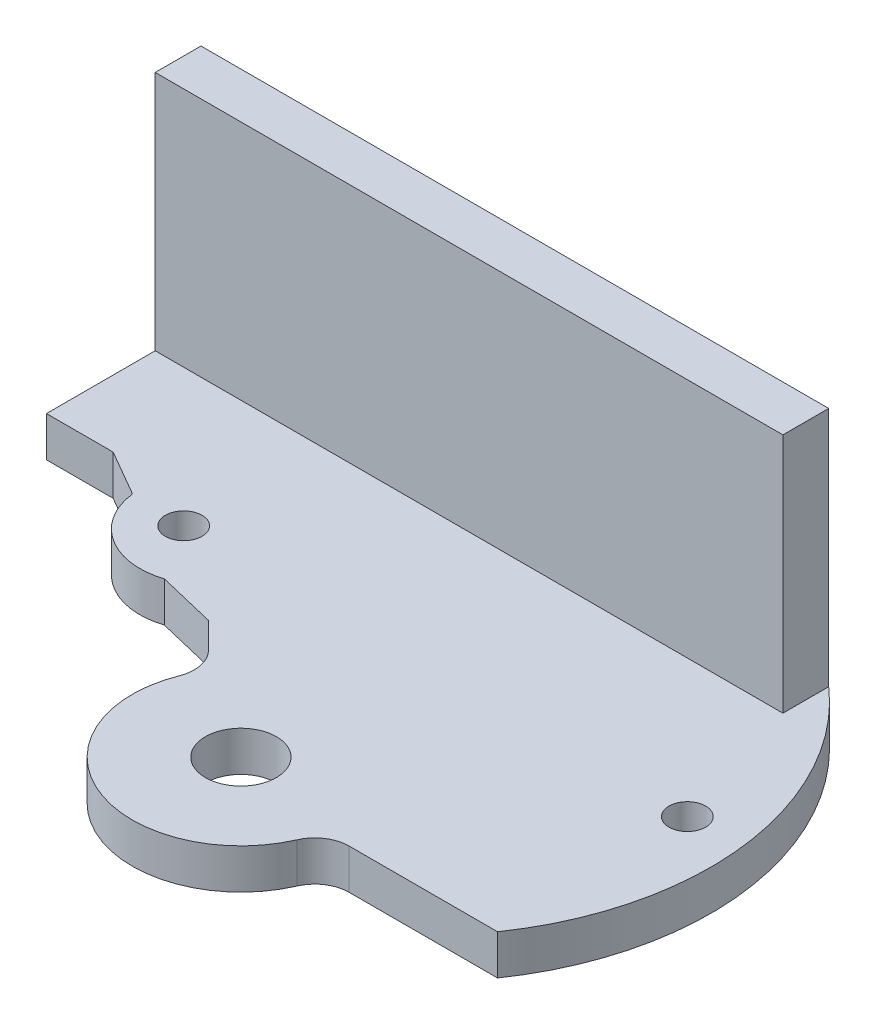
SolidWorks part; units mm, degrees
ref_plane "Alzado" through (0, 0, 0) normal (0, 0, 1) x (1, 0, 0)
ref_plane "Planta" through (0, 0, 0) normal (0, 1, 0) x (1, 0, 0)
ref_plane "Vista lateral" through (0, 0, 0) normal (1, 0, 0) x (0, 0, -1)
sketch "Croquis1" plane through (0, 0, 0) normal (0, 1, 0) x (1, 0, 0)
  line L0 (-35, 32.5) -> (35, -32.5) construction
  line L1 (-35, 32.5) -> (35, 32.5)
  line L2 (-35, 32.5) -> (-35, -32.5)
  line L3 (-35, -32.5) -> (35, -32.5)
  line L4 (35, 32.5) -> (35, -32.5)
  dimension "D1" = 70
  dimension "D2" = 65
extrude "Extruir1" add sketch "Croquis1" along normal blind 3.5
sketch "Croquis2" plane through (0, 3.5, 0) normal (0, 1, 0) x (1, 0, 0)
  line L0 (0, 32.5) -> (0, -32.5) construction
  line L1 (35, 32.5) -> (-35, 32.5) construction
  line L2 (-35, -32.5) -> (35, -32.5) construction
  circle A0 centre (0, -17.5) radius 3.1
  dimension "D1" = 6.2
  dimension "D2" = 15
extrude "Extruir2" cut sketch "Croquis2" against normal blind 5
sketch "Croquis3" plane through (0, 3.5, 0) normal (0, 1, 0) x (1, 0, 0)
  line L0 (0, -32.5) -> (0, 32.5) construction
  line L1 (-35, -32.5) -> (35, -32.5) construction
  line L2 (35, 32.5) -> (-35, 32.5) construction
  line L3 (-32.9868, -32.5) -> (-32.9868, 32.5) construction
  line L4 (-32.9868, 1.5) -> (-12.9615, 1.5)
  line L5 (18.8496, -32.5) -> (18.8496, 32.5) construction
  line L6 (-32.9868, 3.5) -> (18.8496, 3.5) construction
  line L7 (-32.9868, 2) -> (0, 2) construction
  line L8 (-32.9868, 11.5) -> (18.8496, 11.5) construction
  line L9 (0, -17.5) -> (-14.8492, -2.6508) construction
  line L10 (0, -17.5) -> (14.8492, -2.6508) construction
  line L11 (0, 2) -> (18.8496, 2) construction
  line L12 (-32.9868, 2) -> (18.8496, 2) construction
  line L13 (-32.9868, 12) -> (18.8496, 12)
  line L14 (-5.3033, -12.1967) -> (-16.2635, -1.2365) construction
  line L15 (12.9615, 1.5) -> (18.8496, 1.5)
  line L16 (-32.9868, 1.5) -> (18.8496, 1.5) construction
  line L17 (7.9844, -18) -> (22.9946, -18)
  line L18 (-5.9993, -12.2078) -> (-16.6132, -1.5939)
  line L19 (0, -17.5) -> (23, -17.5) construction
  line L20 (7.5, -17.5) -> (23, -17.5) construction
  line L21 (-5.6569, -12.5503) -> (-16.617, -1.5901) construction
  line L22 (7.5, -18) -> (23, -18) construction
  line L23 (-32.9868, 12) -> (-32.9868, 1.5)
  line L24 (18.8496, 12) -> (18.8496, 1.5)
  line L25 (-34.4868, 13.5) -> (20.3496, 13.5)
  line L26 (20.3496, 13.5) -> (20.3496, 0)
  line L27 (17.1464, 0) -> (20.3496, 0)
  line L28 (9.2871, -19.5) -> (24.4182, -19.5)
  line L29 (-7.9812, -12.3473) -> (-18.6805, -1.6479)
  line L30 (-34.4868, 0) -> (-17.1464, 0)
  line L31 (-34.4868, 13.5) -> (-34.4868, 0)
  circle A0 centre (0, -17.5) radius 21 construction
  circle A1 centre (0, -17.5) radius 7.5 construction
  arc A2 (-12.9615, 1.5) -> (-16.6132, -1.5939) centre (0, -17.5) ccw
  circle A3 centre (0, -17.5) radius 23 construction
  arc A4 (-5.9993, -12.2078) -> (7.9844, -18) centre (0, -17.5) ccw
  arc A5 (22.9946, -18) -> (12.9615, 1.5) centre (0, -17.5) ccw
  arc A6 (24.4182, -19.5) -> (17.1464, 0) centre (0, -17.5) ccw
  arc A7 (-7.9812, -12.3473) -> (9.2871, -19.5) centre (0, -17.5) ccw
  arc A8 (-17.1464, 0) -> (-18.6805, -1.6479) centre (0, -17.5) ccw
  dimension "D3" = 42
  dimension "D8" = 15
  dimension "D9" = 46
  dimension "D14" = 0.5
  dimension "D2" = 51.8364
  dimension "D6" = 90
  dimension "D7" = 45
  dimension "D1" = 32.9868
  dimension "D4" = 1.5
  dimension "D5" = 9.5
  dimension "D10" = 2
  dimension "D11" = 0.5
  dimension "D12" = 0.5
  dimension "D13" = 0.5
  dimension "D15" = 1.5
extrude "Extruir3" add sketch "Croquis3" along normal blind 10
sketch "Croquis4" plane through (0, 3.5, 0) normal (0, 1, 0) x (1, 0, 0)
  line L0 (-34.4868, 0) -> (-17.1464, 0) construction
  line L1 (-34.4868, 13.5) -> (-34.4868, 0) construction
  line L2 (20.3496, 13.5) -> (-34.4868, 13.5) construction
  line L3 (20.3496, 0) -> (20.3496, 13.5) construction
  line L4 (17.1464, 0) -> (20.3496, 0) construction
  line L5 (9.2871, -19.5) -> (24.4182, -19.5) construction
  line L6 (-18.6805, -1.6479) -> (-7.9812, -12.3473) construction
  line L7 (-34.4868, 0) -> (-17.1464, 0)
  line L8 (-34.4868, 13.5) -> (-34.4868, 0)
  line L9 (20.3496, 13.5) -> (-34.4868, 13.5)
  line L10 (20.3496, 0) -> (20.3496, 13.5)
  line L11 (17.1464, 0) -> (20.3496, 0)
  line L12 (9.2871, -19.5) -> (24.4182, -19.5)
  line L13 (-18.6805, -1.6479) -> (-7.9812, -12.3473)
  arc A0 (-17.1464, 0) -> (-18.6805, -1.6479) centre (0, -17.5) ccw construction
  arc A1 (24.4182, -19.5) -> (17.1464, 0) centre (0, -17.5) ccw construction
  arc A2 (-7.9812, -12.3473) -> (9.2871, -19.5) centre (0, -17.5) ccw construction
  arc A3 (-17.1464, 0) -> (-18.6805, -1.6479) centre (0, -17.5) ccw
  arc A4 (24.4182, -19.5) -> (17.1464, 0) centre (0, -17.5) ccw
  arc A5 (-7.9812, -12.3473) -> (9.2871, -19.5) centre (0, -17.5) ccw
extrude "Extruir4" cut sketch "Croquis4" against normal blind 10 flip side to cut
fillet "Redondeo1" radius 3 4 edges at (9.2871, 6.75, 19.5) (-7.9812, 6.75, 12.3473) (7.9844, 8.5, 18) (-5.9993, 8.5, 12.2078)
sketch "Croquis5" plane through (0, 0, 0) normal (0, -1, 0) x (1, 0, 0)
  line L0 (-18.6805, 1.6479) -> (-9.5151, 10.8133) construction
  line L1 (-34.4868, 0) -> (-17.1464, 0) construction
  line L2 (-18.6805, 1.6479) -> (-14.4379, 5.8906)
  line L3 (-24.4498, 0) -> (-17.1464, 0)
  line L4 (20.3496, 0) -> (20.3496, -13.5) construction
  line L5 (17.1464, 0) -> (20.3496, 0) construction
  line L6 (20.3496, 0) -> (20.3496, -13.5)
  line L7 (17.1464, 0) -> (20.3496, 0)
  arc A0 (-14.4379, 5.8906) -> (-24.4498, 0) centre (-18.6805, 1.6479) ccw
  arc A1 (-18.6805, 1.6479) -> (-17.1464, 0) centre (0, 17.5) ccw construction
  arc A2 (-18.6805, 1.6479) -> (-17.1464, 0) centre (0, 17.5) ccw
  arc A3 (24.4182, 19.5) -> (20.3496, -13.5) centre (3.8531, 5.2847) cw
  arc A4 (17.1464, 0) -> (24.4182, 19.5) centre (0, 17.5) ccw construction
  arc A5 (17.1464, 0) -> (24.4182, 19.5) centre (0, 17.5) ccw
  dimension "D1" = 12
  dimension "D2" = 25
extrude "Extruir5" add sketch "Croquis5" against normal up to surface (13.5 mm away) up to face at (-1.8278, 13.5, 5.5887)
chamfer "Chaflán1" distance 5 angle 45 2 edges at (-14.4379, 6.75, 5.8906) (-24.4498, 6.75, 0) first distance on face at (-20.5835, 6.75, 4.8823) first distance on face at (-29.4683, 6.75, 0)
sketch "Croquis6" plane through (0, 13.5, 0) normal (0, 1, 0) x (1, 0, 0)
  line L7 (-34.4868, 13.5) -> (-34.4868, 0)
  line L8 (-34.4868, 0) -> (-28.6614, 0)
  line L9 (-28.6614, 0) -> (-24.6424, -2.3231)
  line L10 (-16.83, -7.3554) -> (-11.7523, -8.5761)
  line L11 (-11.7523, -8.5761) -> (-9.5151, -10.8133)
  line L12 (11.4564, -19.5) -> (24.4182, -19.5)
  line L13 (20.3496, 13.5) -> (-34.4868, 13.5)
  line L14 (-34.4868, 13.5) -> (-34.4868, 0)
  line L15 (-34.4868, 0) -> (-28.6614, 0)
  line L16 (-28.6614, 0) -> (-24.6424, -2.3231)
  line L17 (-16.83, -7.3554) -> (-11.7523, -8.5761)
  line L18 (-11.7523, -8.5761) -> (-9.5151, -10.8133)
  line L19 (11.4564, -19.5) -> (24.4182, -19.5)
  line L20 (20.3496, 13.5) -> (-34.4868, 13.5)
  arc A5 (-24.6424, -2.3231) -> (-16.83, -7.3554) centre (-18.6805, -1.6479) ccw
  arc A6 (-8.8437, -14.0303) -> (-9.5151, -10.8133) centre (-11.6365, -12.9346) ccw
  arc A7 (-8.8437, -14.0303) -> (8.7069, -21.3) centre (0, -17.5) ccw
  arc A8 (11.4564, -19.5) -> (8.7069, -21.3) centre (11.4564, -22.5) ccw
  arc A9 (24.4182, -19.5) -> (20.3496, 13.5) centre (3.8531, -5.2847) ccw
  arc A10 (-24.6424, -2.3231) -> (-16.83, -7.3554) centre (-18.6805, -1.6479) ccw
  arc A11 (-8.8437, -14.0303) -> (-9.5151, -10.8133) centre (-11.6365, -12.9346) ccw
  arc A12 (-8.8437, -14.0303) -> (8.7069, -21.3) centre (0, -17.5) ccw
  arc A13 (11.4564, -19.5) -> (8.7069, -21.3) centre (11.4564, -22.5) ccw
  arc A14 (24.4182, -19.5) -> (20.3496, 13.5) centre (3.8531, -5.2847) ccw
  dimension "D1" = 0
extrude "Extruir6" add sketch "Croquis6" along normal blind 3.5 separate body
sketch "Croquis7" plane through (0, 17, 0) normal (0, 1, 0) x (1, 0, 0)
  line L0 (20.3496, 13.5) -> (-34.4868, 13.5) construction
  circle A0 centre (-20, -2.5) radius 1.6
  circle A1 centre (24, -2.5) radius 1.6
  dimension "D1" = 3.2
  dimension "D2" = 16
  dimension "D3" = 20
  dimension "D4" = 24
extrude "Extruir7" cut sketch "Croquis7" against normal through all
sketch "Croquis8" plane through (0, 17, 0) normal (0, 1, 0) x (1, 0, 0)
  circle A0 centre (0, -17.5) radius 3.1 construction
  circle A1 centre (0, -17.5) radius 3.1
extrude "Extruir8" cut sketch "Croquis8" against normal blind 5
sketch "Croquis9" plane through (0, 13.5, 0) normal (0, 1, 0) x (1, 0, 0)
  line L0 (18.8496, 1.5) -> (18.8496, 12) construction
  line L1 (18.8496, 1.5) -> (18.8496, 12)
  line L2 (19.5496, 1.5) -> (19.5496, 12)
  line L3 (18.8496, 12) -> (19.5496, 12)
  line L4 (18.8496, 1.5) -> (19.5496, 1.5)
  dimension "D1" = 0.7
extrude "Extruir9" cut sketch "Croquis9" against normal up to surface (10 mm away) up to face at (-1.6185, 3.5, 4.8365)
sketch "Croquis10" plane through (19.5496, 0, 0) normal (-1, 0, 0) x (0, 0, 1)
  line L0 (-5.875, 13.5) -> (-5.875, 3.5) construction
  line L3 (-1.5, 13.5) -> (-12, 13.5) construction
  line L4 (-12, 3.5) -> (-12, 13.5) construction
  line L5 (-5.875, 13.5) -> (-12, 3.5) construction
  line L6 (-12, 3.5) -> (-1.5, 3.5) construction
  line L7 (-8.9375, 8.5) -> (-12, 13.5) construction
  line L8 (19.5, 13.5) -> (-13.5, 13.5) construction
  line L10 (-7.4062, 11) -> (-10.4687, 11)
  line L11 (-7.4062, 11) -> (-7.4062, 6)
  line L12 (-7.4062, 6) -> (-10.4687, 6)
  line L13 (-10.4687, 11) -> (-10.4687, 6)
  dimension "D1" = 6.125
  dimension "D2" = 5
  dimension "D3" = 3.0625
extrude "Extruir10" cut sketch "Croquis10" against normal blind 10 and the other way through all
delete or keep bodies "Sólido-Eliminar1" type delete bodies bodies 111
sketch "Croquis11" plane through (0, 0, -13.5) normal (0, 0, -1) x (-1, 0, 0)
  line L0 (34.4868, 17) -> (34.4868, 38.056)
  line L2 (-20.3496, 38.056) -> (-20.3496, 17)
  line L3 (-20.3496, 17) -> (34.4868, 17)
  line L4 (34.4868, 38.056) -> (-20.3496, 38.056)
  dimension "D2" = 21.056
extrude "Saliente-Extruir1" add sketch "Croquis11" against normal blind 4
